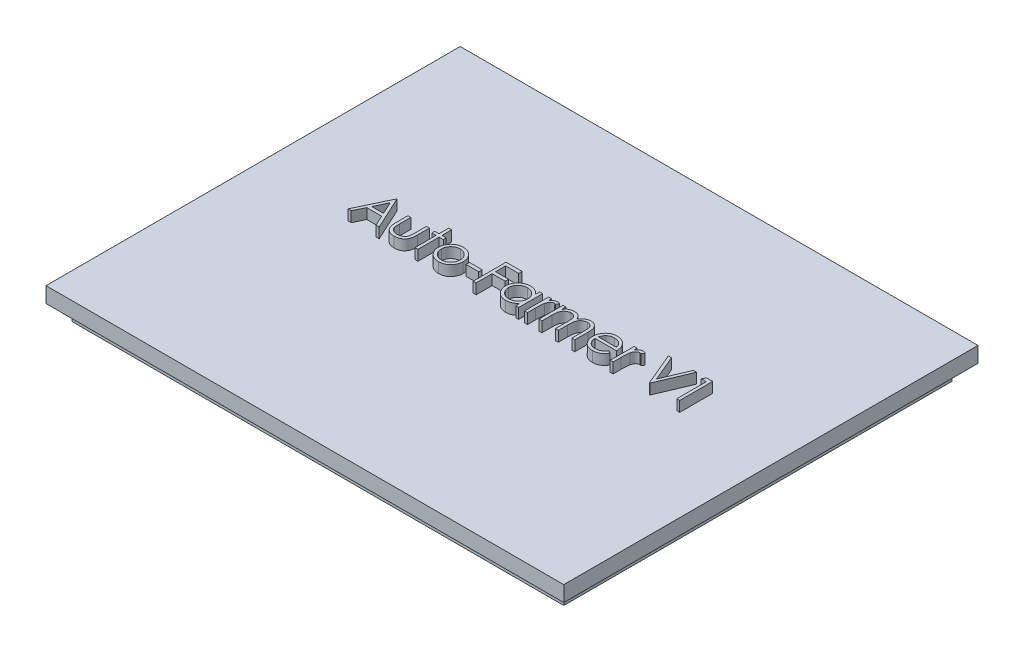
SolidWorks part; units mm, degrees
ref_plane "Front" through (0, 0, 0) normal (0, 0, 1) x (1, 0, 0)
ref_plane "Top" through (0, 0, 0) normal (0, 1, 0) x (1, 0, 0)
ref_plane "Right" through (0, 0, 0) normal (1, 0, 0) x (0, 0, -1)
sketch "Sketch1" plane through (0, 0, 0) normal (0, 1, 0) x (1, 0, 0)
  line L1 (-50, -40) -> (50, -40)
  line L2 (-50, -40) -> (-50, 40)
  line L3 (-50, 40) -> (50, 40)
  line L4 (50, -40) -> (50, 40)
  line L5 (-50, -40) -> (50, 40) construction
  line L6 (-50, 40) -> (50, -40) construction
  point P0 (0, 0)
  dimension "D1" = 100
  dimension "D2" = 80
extrude "Boss-Extrude1" add sketch "Sketch1" along normal blind 3
sketch "Sketch2" plane through (0, 0, 0) normal (0, -1, 0) x (1, 0, 0)
  line L1 (-47.5, -37.5) -> (47.5, -37.5)
  line L2 (-47.5, -37.5) -> (-47.5, 37.5)
  line L3 (-47.5, 37.5) -> (47.5, 37.5)
  line L4 (47.5, -37.5) -> (47.5, 37.5)
  line L5 (-47.5, -37.5) -> (47.5, 37.5) construction
  line L6 (-47.5, 37.5) -> (47.5, -37.5) construction
  point P0 (0, 0)
  dimension "D1" = 95
  dimension "D2" = 75
extrude "Boss-Extrude2" add sketch "Sketch2" along normal blind 3
sketch "Sketch3" plane through (0, 3, 0) normal (0, 1, 0) x (1, 0, 0)
  line L0 (-50, 40) -> (-50, -40) construction
  text T0 "Auto-Farmer V1"
  dimension "D1" = 18
extrude "Boss-Extrude3" add sketch "Sketch3" along normal blind 2
